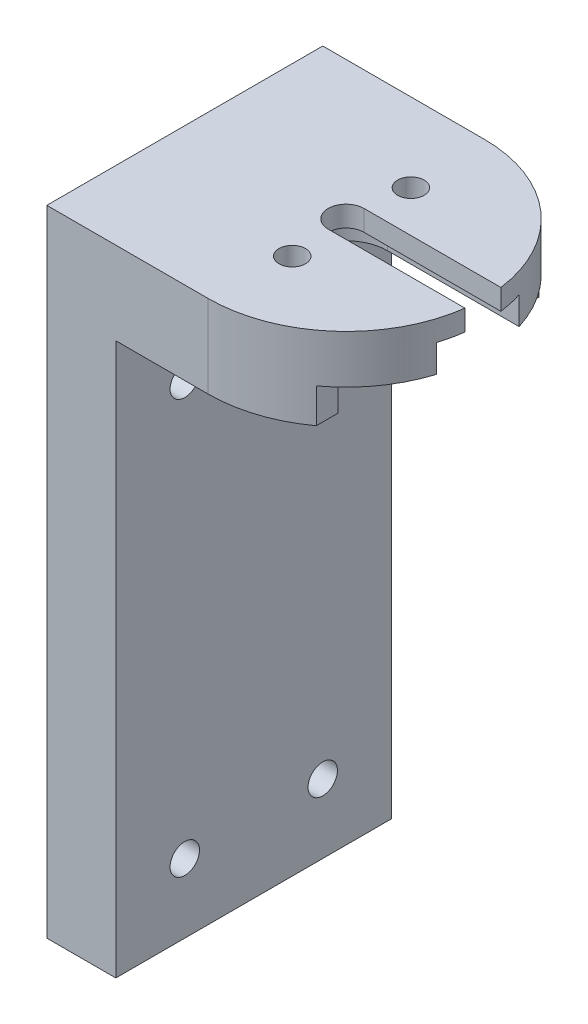
SolidWorks part; units mm, degrees
ref_plane "Front Plane" through (0, 0, 0) normal (0, 0, 1) x (1, 0, 0)
ref_plane "Top Plane" through (0, 0, 0) normal (0, 1, 0) x (1, 0, 0)
ref_plane "Right Plane" through (0, 0, 0) normal (1, 0, 0) x (0, 0, -1)
sketch "Sketch1" plane through (0, 0, 0) normal (0, 0, 1) x (1, 0, 0)
  line L1 (-22.352, -53.975) -> (-16.002, -53.975)
  line L2 (-16.002, -53.975) -> (-16.002, -3.175)
  line L3 (-16.002, -3.175) -> (0, -3.175)
  line L4 (0, -3.175) -> (0, 0)
  line L5 (0, 0) -> (25.654, 0)
  line L7 (25.654, 0) -> (25.654, 4.445)
  line L8 (25.654, 4.445) -> (-22.352, 4.445)
  line L9 (-22.352, 4.445) -> (-22.352, -53.975)
  dimension "D1" = 58.42
  dimension "D2" = 48.006
  dimension "D3" = 22.352
  dimension "D4" = 6.35
  dimension "D5" = 0
  dimension "D6" = 4.445
  dimension "D7" = 3.175
extrude "Boss-Extrude1" add sketch "Sketch1" along normal blind 25.4
sketch "Sketch2" plane through (0, 0, 0) normal (1, 0, 0) x (0, 0, -1)
  line L0 (-25.4, 0) -> (0, 0) construction
  line L1 (-4.445, 0) -> (-20.955, 0)
  line L2 (-4.445, 0) -> (-4.445, -1.9646)
  line L3 (-4.445, -1.9646) -> (-20.955, -1.9646)
  line L4 (-20.955, 0) -> (-20.955, -1.9646)
  line L5 (-25.4, -3.175) -> (0, -3.175) construction
  line L6 (-20.955, -1.9646) -> (-4.445, -1.9646)
  line L7 (-20.955, -1.9646) -> (-20.955, -3.175)
  line L8 (-20.955, -3.175) -> (-4.445, -3.175)
  line L9 (-4.445, -1.9646) -> (-4.445, -3.175)
  line L10 (0, -3.175) -> (0, 0) construction
  line M2 (0, 0) -> (-25.4, 0)
  dimension "D1" = 16.51
  dimension "D2" = 1.9646
  dimension "D3" = 16.51
  dimension "D4" = 0
  dimension "D5" = 4.445
extrude "Cut-Extrude1" cut sketch "Sketch2" against normal up to surface (16.002 mm away) contours L4 L3 L2 M2 | L8 L9 L6 L7 region at (0, -0.9823, 12.7) up to face at (-16.002, -28.575, 12.7)
sketch "Sketch3" plane through (0, 0, 0) normal (0, -1, 0) x (1, 0, 0)
  line L0 (-7.502, 12.7) -> (11.5, 12.7) construction
  line L1 (-7.502, 14.351) -> (11.5, 14.351)
  line L2 (-7.502, 11.049) -> (11.5, 11.049)
  line L3 (0, 4.445) -> (0, 0) construction
  line L5 (-16.002, 4.445) -> (-16.002, 20.955) construction
  line L6 (0, 0) -> (25.654, 0) construction
  arc A0 (-7.502, 14.351) -> (-7.502, 11.049) centre (-7.502, 12.7) ccw
  arc A1 (11.5, 11.049) -> (11.5, 14.351) centre (11.5, 12.7) ccw
  point P2 (1.999, 12.7)
  dimension "D1" = 3.302
  dimension "D2" = 11.5
  dimension "D3" = 8.5
  dimension "D4" = 12.7
extrude "Cut-Extrude2" cut sketch "Sketch3" against normal up to surface (4.445 mm away) up to face at (1.651, 4.445, 12.7)
sketch "Sketch4" plane through (0, 0, 0) normal (0, -1, 0) x (1, 0, 0)
  line L0 (-7.502, 12.7) -> (11.5, 12.7) construction
  line L1 (-7.502, 16.51) -> (11.5, 16.51)
  line L2 (-7.502, 8.89) -> (11.5, 8.89)
  arc A0 (-7.502, 16.51) -> (-7.502, 8.89) centre (-7.502, 12.7) ccw
  arc A1 (11.5, 8.89) -> (11.5, 16.51) centre (11.5, 12.7) ccw
  point P4 (1.999, 12.7)
  dimension "D1" = 7.62
extrude "Cut-Extrude3" cut sketch "Sketch4" against normal blind 2.54
fillet "Fillet1" radius 12.7 2 edges at (25.654, 2.2225, 0) (25.654, 2.2225, 25.4)
hole_wizard "#2 Clearance Hole1" positions "Sketch6" profile "Sketch7" hole size "#2" standard "ANSI Inch"
sketch "Sketch6" plane through (0, 4.445, 0) normal (0, 1, 0) x (1, 0, 0)
  line L0 (-16.002, -4.445) -> (-16.002, -20.955) construction
  arc A0 (-7.502, -11.049) -> (-7.502, -14.351) centre (-7.502, -12.7) ccw construction
  point P0 (-7.002, -18.16)
  point P2 (-7.002, -7.24)
  point P7 (-9.153, -12.7)
  dimension "D1" = 9
  dimension "D2" = 9
  dimension "D3" = 10.92
  dimension "D4" = 5.46
sketch "Sketch7" plane through (-7.002, 4.445, 18.16) normal (1, 0, 0) x (0, 0, 1)
  line L0 (0, 0) -> (0, 26.1326)
  line L1 (0, 26.1326) -> (1.2192, 25.4)
  line L2 (1.2192, 25.4) -> (1.2192, 0)
  line L5 (1.2192, 0) -> (0, 0)
  line L10 (0, 26.1326) -> (-1.2192, 25.4) construction
  line L11 (0, -6.35) -> (0, 107.95) construction
  dimension "Hole Dia." = 2.4384
  dimension "Hole Depth" = 25.4
  dimension "Drill Angle" = 118
hole_wizard "#6-32 Tapped Hole1" positions "Sketch9" profile "Sketch8" tap size "#6-32" standard "ANSI Inch"
sketch "Sketch9" plane through (-22.352, 0, 0) normal (-1, 0, 0) x (0, 0, 1)
  line L0 (0, 4.445) -> (0, -53.975) construction
  line L1 (25.4, 4.445) -> (25.4, -53.975) construction
  line L2 (25.4, -53.975) -> (0, -53.975) construction
  point P0 (6.35, -9.525)
  point P2 (19.05, -9.525)
  point P4 (6.35, -47.625)
  point P6 (19.05, -47.625)
  dimension "D1" = 6.35
  dimension "D2" = 6.35
  dimension "D3" = 6.35
  dimension "D4" = 6.35
  dimension "D5" = 38.1
  dimension "D6" = 38.1
  dimension "D7" = 6.35
  dimension "D8" = 6.35
sketch "Sketch8" plane through (-22.352, -9.525, 6.35) normal (0, 1, 0) x (0, 0, 1)
  line L0 (0, 0) -> (0, 10.2107)
  line L1 (0, 10.2107) -> (1.3525, 9.398)
  line L2 (1.3525, 9.398) -> (1.3525, 0)
  line L5 (1.3525, 0) -> (0, 0)
  line L10 (0, 10.2107) -> (-1.3526, 9.398) construction
  line L11 (0, -6.35) -> (0, 107.95) construction
  dimension "Tap Drill Dia." = 2.7051
  dimension "Tap Drill Depth" = 9.398
  dimension "Drill Angle" = 118
sketch "Sketch10" plane through (0, 4.445, 0) normal (0, 1, 0) x (1, 0, 0)
  line L0 (12.954, -25.4) -> (-22.352, -25.4) construction
  line L1 (12.954, 0) -> (-22.352, 0) construction
  line L2 (-7.502, -25.4) -> (30.598, -25.4)
  line L3 (30.598, -25.4) -> (30.598, 0)
  line L4 (30.598, 0) -> (-7.502, 0)
  arc A0 (-7.502, -25.4) -> (-7.502, 0) centre (-7.502, -12.7) ccw
  dimension "D1" = 12.7
  dimension "D2" = 38.1
extrude "Cut-Extrude4" cut sketch "Sketch10" against normal up to surface (7.62 mm away) up to face at (-8.001, -3.175, 23.1775)
